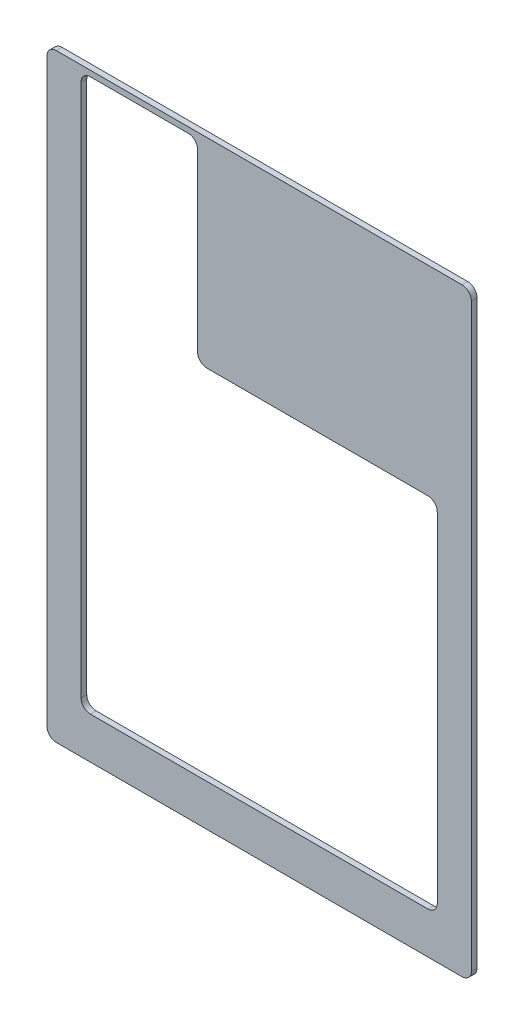
SolidWorks part; units mm, degrees
ref_plane "Front Plane" through (0, 0, 0) normal (0, 0, 1) x (1, 0, 0)
ref_plane "Top Plane" through (0, 0, 0) normal (0, 1, 0) x (1, 0, 0)
ref_plane "Right Plane" through (0, 0, 0) normal (1, 0, 0) x (0, 0, -1)
sketch "Sketch1" plane through (0, 0, 0) normal (0, 0, 1) x (1, 0, 0)
  line L1 (-161.925, -228.6) -> (161.925, -228.6)
  line L2 (-161.925, -228.6) -> (-161.925, 228.6)
  line L3 (-161.925, 228.6) -> (161.925, 228.6)
  line L4 (161.925, -228.6) -> (161.925, 228.6)
  line L5 (-161.925, -228.6) -> (161.925, 228.6) construction
  line L6 (-161.925, 228.6) -> (161.925, -228.6) construction
  point P0 (0, 0)
  dimension "D1" = 323.85
  dimension "D2" = 457.2
extrude "Boss-Extrude1" add sketch "Sketch1" along normal blind 4.3434
sketch "Sketch2" plane through (0, 0, 4.3434) normal (0, 0, 1) x (1, 0, 0)
  line L0 (0, 228.6) -> (0, -228.6) construction
  line L1 (-135.89, -196.85) -> (135.89, -196.85)
  line L2 (-135.89, -196.85) -> (-135.89, 76.2)
  line L3 (-135.89, 76.2) -> (135.89, 76.2)
  line L4 (135.89, -196.85) -> (135.89, 76.2)
  line L5 (-135.89, -196.85) -> (135.89, 76.2) construction
  line L6 (-135.89, 76.2) -> (135.89, -196.85) construction
  line L7 (161.925, 228.6) -> (-161.925, 228.6) construction
  line L8 (-161.925, -228.6) -> (161.925, -228.6) construction
  point P0 (0, -65.2276)
  point P12 (0, -60.325)
  dimension "D1" = 271.78
  dimension "D2" = 273.05
  dimension "D3" = 31.75
extrude "Cut-Extrude1" cut sketch "Sketch2" against normal through all
fillet "Fillet1" radius 7.1437 8 edges at (135.89, -196.85, 2.1717) (135.89, 76.2, 2.1717) (-135.89, 76.2, 2.1717) (-135.89, -196.85, 2.1717) (-161.925, -228.6, 2.1717) (161.925, -228.6, 2.1717) (161.925, 228.6, 2.1717) (-161.925, 228.6, 2.1717)
sketch "Sketch4" plane through (0, 0, 4.3434) normal (0, 0, 1) x (1, 0, 0)
  line L0 (-135.89, 39.3453) -> (-135.89, 224.2566)
  line L1 (-135.89, 39.3453) -> (-46.99, 39.3453)
  line L2 (-135.89, 224.2566) -> (-46.99, 224.2566)
  line L3 (-46.99, 39.3453) -> (-46.99, 224.2566)
  line L4 (-135.89, 69.0562) -> (-135.89, -189.7063) construction
  line L6 (154.7812, 228.6) -> (-154.7813, 228.6) construction
  dimension "D1" = 88.9
  dimension "D2" = 4.3434
extrude "Cut-Extrude3" cut sketch "Sketch4" against normal through all
fillet "Fillet2" radius 7.1437 3 edges at (-46.99, 76.2, 2.1717) (-46.99, 224.2566, 2.1717) (-135.89, 224.2566, 2.1717)
